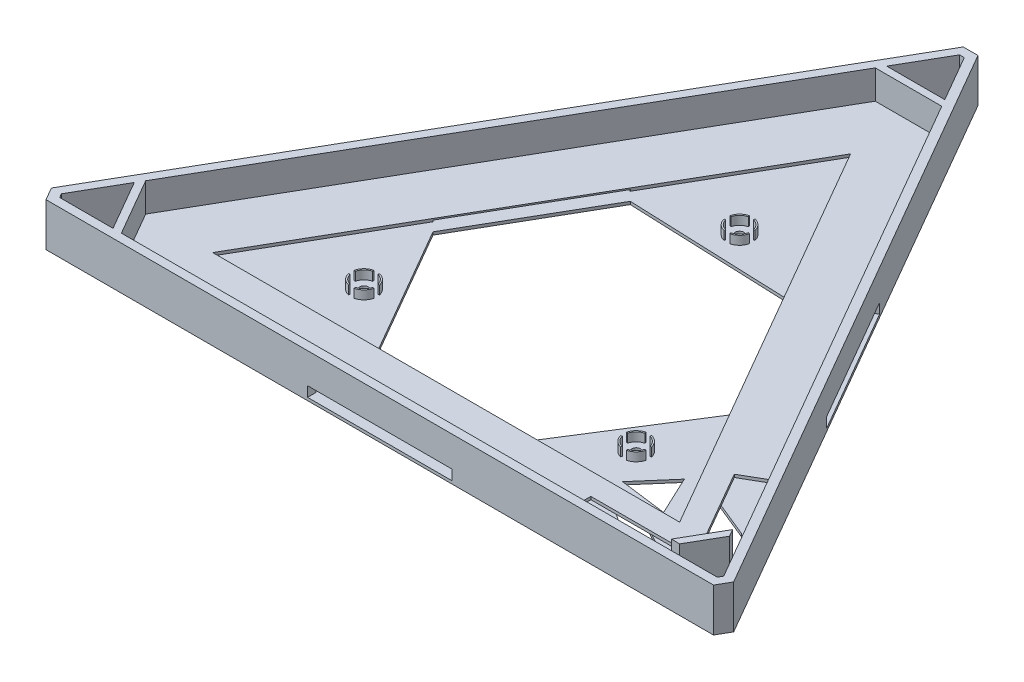
SolidWorks part; units mm, degrees
ref_plane "Front Plane" through (0, 0, 0) normal (0, 0, 1) x (1, 0, 0)
ref_plane "Top Plane" through (0, 0, 0) normal (0, 1, 0) x (1, 0, 0)
ref_plane "Right Plane" through (0, 0, 0) normal (1, 0, 0) x (0, 0, -1)
sketch "Sketch1" plane through (0, 0, 0) normal (0, 1, 0) x (1, 0, 0)
  line L0 (351.2729, 67.6655) -> (468.273, -134.9846)
  line L1 (347.2728, 67.6655) -> (347.2728, 65.1655) construction
  line L2 (409.773, -33.6595) -> (407.6079, -34.9095) construction
  line L3 (468.273, -134.9846) -> (464.2732, -141.9124)
  line L4 (230.2733, -141.9124) -> (464.2732, -141.9124)
  line L5 (230.2733, -141.9124) -> (226.2727, -134.9842)
  line L6 (226.2727, -134.9842) -> (343.2728, 67.6655)
  line L7 (353.4142, 63.9567) -> (351.2491, 62.7067) construction
  line L8 (347.2733, -141.9124) -> (347.2733, -139.4124) construction
  line L9 (231.7167, -139.4124) -> (462.8299, -139.4124)
  line L10 (284.7727, -33.6594) -> (286.9378, -34.9094) construction
  line L11 (344.7161, 65.1655) -> (349.8295, 65.1655)
  line L12 (465.3862, -134.9846) -> (349.8295, 65.1655)
  line L13 (466.2731, -138.4485) -> (464.1081, -137.1985) construction
  line L14 (462.8299, -139.4124) -> (465.3862, -134.9846)
  line L15 (229.1594, -134.9842) -> (344.7161, 65.1655)
  line L16 (229.1594, -134.9842) -> (231.7167, -139.4124)
  line L17 (286.9378, -34.9094) -> (287.3708, -35.1594) construction
  line L18 (230.438, -137.1983) -> (230.871, -136.9483) construction
  line L19 (232.0053, -138.9123) -> (229.7368, -134.9842)
  line L20 (343.2728, 67.6655) -> (351.2729, 67.6655)
  line L21 (345.0048, 64.6655) -> (229.7368, -134.9842)
  line L22 (349.5409, 64.6655) -> (345.0048, 64.6655)
  line L23 (249.0568, -126.4468) -> (246.8918, -127.697) construction
  line L24 (407.6079, -34.9095) -> (407.1749, -35.1595) construction
  line L26 (233.4463, -136.4089) -> (251.9226, -136.4093)
  line L27 (464.8089, -134.9846) -> (462.5412, -138.9123)
  line L28 (462.5412, -138.9123) -> (232.0053, -138.9123)
  line L29 (251.9226, -136.4093) -> (241.8609, -118.9847)
  line L30 (241.8609, -118.9847) -> (232.6236, -134.9842)
  line L31 (232.6236, -134.9842) -> (233.4463, -136.4089)
  line L33 (287.3708, -35.1594) -> (289.5359, -36.4094) construction
  line L34 (254.8093, -136.4089) -> (243.3042, -116.4848)
  line L35 (335.7675, 43.666) -> (243.3042, -116.4848)
  line L36 (358.7782, 43.666) -> (335.7675, 43.666)
  line L38 (289.5359, -36.4094) -> (306.8564, -46.4094) construction
  line L41 (461.939, -134.9846) -> (461.1164, -136.4093)
  line L42 (347.2688, -136.4172) -> (347.2688, -116.4172) construction
  line L43 (442.6021, -136.4093) -> (452.6999, -118.9847)
  line L44 (245.2636, -119.878) -> (249.0568, -126.4468) construction
  line L45 (452.6999, -118.9847) -> (461.939, -134.9846)
  line L48 (461.1164, -136.4093) -> (442.6021, -136.4093)
  line L49 (405.0134, -36.4027) -> (387.6936, -46.404) construction
  line L50 (306.8564, -46.4094) -> (466.2731, -138.4485) construction
  line L51 (357.3348, 46.166) -> (337.2109, 46.166)
  line L52 (337.2109, 46.166) -> (346.4484, 62.1659)
  line L53 (346.4484, 62.1659) -> (348.0966, 62.164)
  line L54 (348.0966, 62.164) -> (357.3348, 46.166)
  line L55 (228.273, -138.4483) -> (387.6936, -46.404) construction
  line L56 (347.2688, -116.4172) -> (347.2728, 43.666) construction
  line L57 (266.4391, -116.428) -> (428.1137, -116.4172)
  line L58 (347.2736, 23.6092) -> (428.1137, -116.4172)
  line L59 (266.4391, -116.428) -> (347.2736, 23.6092)
  line L60 (439.7283, -136.4254) -> (439.7283, -132.9254) construction
  line L61 (451.2487, -116.4715) -> (448.6507, -117.9717) construction
  line L62 (452.6999, -118.9847) -> (358.7782, 43.666)
  line L63 (442.6021, -136.4093) -> (254.8093, -136.4089)
  line L64 (441.749, -132.9254) -> (444.621, -132.9254)
  line L65 (448.6507, -117.9717) -> (450.9647, -121.979) construction
  line L66 (449.5167, -119.4714) -> (450.9647, -121.979)
  line L67 (441.749, -132.9254) -> (449.5167, -119.4714)
  line L68 (450.9647, -121.979) -> (444.621, -132.9254)
  line L69 (461.939, -134.9846) -> (427.2809, -114.9747) construction
  line L70 (461.1164, -136.4093) -> (426.4891, -116.4173) construction
  line L73 (405.0134, -134.9846) -> (439.7283, -134.9846)
  line L74 (405.0134, -134.9846) -> (405.0134, -124.0609)
  line L75 (405.0134, -124.0609) -> (439.7283, -124.0609)
  line L76 (439.7283, -134.9846) -> (439.7283, -124.0609)
  line L77 (405.0134, -124.0609) -> (430.3202, -80.2282) construction
  line L78 (405.0134, -134.9846) -> (433.4739, -85.6896) construction
  line L79 (461.1164, -136.4093) -> (424.3464, -72.7321) construction
  line L80 (432.6513, -87.1143) -> (423.1904, -92.5775)
  line L81 (432.6513, -87.1143) -> (450.1194, -117.365)
  line L82 (423.1904, -92.5775) -> (440.6585, -122.8281)
  line L83 (450.1194, -117.365) -> (440.6585, -122.8281)
  point P13 (407.6079, -34.9095)
  point P20 (464.1081, -137.1985)
  point P23 (347.2733, -139.4124)
  point P25 (347.2732, -141.9124)
  point P27 (347.2728, 65.1655)
  point P31 (286.9378, -34.9094)
  point P37 (287.3708, -35.1594)
  point P39 (230.871, -136.9483)
  point P41 (347.2728, 64.6655)
  point P45 (407.1749, -35.1595)
  point P50 (246.8918, -127.697)
  point P56 (289.5359, -36.4094)
  point P58 (249.0568, -126.4468)
  point P60 (347.2728, 43.666)
  point P62 (345.0048, -136.4089)
  point P64 (445.4885, -126.4485)
  point P71 (447.651, -127.697)
  point P77 (347.2728, 46.166)
  point P84 (347.2688, -116.4172)
  point P87 (387.6936, -46.404)
  point P89 (306.8564, -46.4094)
  point P100 (405.0134, -36.4027)
  dimension "D1" = 2.5
  dimension "D2" = 2.5
  dimension "D3" = 2.5
  dimension "D4" = 2.5
  dimension "D5" = 2.5
  dimension "D6" = 2.5
  dimension "D7" = 0.5
  dimension "D8" = 0.5
  dimension "D9" = 0.5
  dimension "D10" = 2.5
  dimension "D11" = 2.5
  dimension "D12" = 20
  dimension "D13" = 20
  dimension "D14" = 20
  dimension "D15" = 3.5
  dimension "D16" = 3
extrude "Boss-Extrude1" add sketch "Sketch1" along normal blind 1 contours L36 L35 L34 L57 L59 L58 region at (251.4484, 0, 125.0658)
extrude "Boss-Extrude2" add sketch "Sketch1<9>" along normal blind 11 contours L28 L27 L22 L21 L19 L31 L30 L29 L26 L34 L35 L36 L41 L48 L43 L45 L53 L54 L51 L52 | L68 L64 L67 L66 region at (230.7087, 0, 137.042)
sketch "Sketch1<9>" plane through (0, 0, 0) normal (0, 1, 0) x (1, 0, 0) same geometry as "Sketch1"
extrude "Boss-Extrude3" add sketch "Sketch1<10>" along normal blind 5 and the other way blind 3 contours L28 L27 L22 L21 L19 L31 L30 L29 L26 L34 L35 L36 L41 L48 L43 L45 L53 L54 L51 L52 | L68 L64 L67 L66 region at (230.7087, 0, 137.042)
sketch "Sketch1<10>" plane through (0, 0, 0) normal (0, 1, 0) x (1, 0, 0) same geometry as "Sketch1"
sketch "Sketch3" plane through (290.5896, 0, -167.772) normal (0.866, 0, -0.5) x (-0.5, 0, -0.866)
  line L1 (-261.593, -6.5) -> (-211.593, -6.5)
  line L2 (-261.593, -6.5) -> (-261.593, 0.5)
  line L3 (-261.593, 0.5) -> (-211.593, 0.5)
  line L4 (-211.593, -6.5) -> (-211.593, 0.5)
  line L5 (-261.593, -6.5) -> (-211.593, 0.5) construction
  line L6 (-261.593, 0.5) -> (-211.593, -6.5) construction
  point P0 (-236.593, -3)
  dimension "D1" = 50
  dimension "D2" = 7
extrude "Cut-Extrude3" cut sketch "Sketch3" against normal blind 25
sketch "Sketch5" plane through (0, 0, 139.4124) normal (0, 0, 1) x (1, 0, 0)
  line L0 (231.7167, -3) -> (462.8299, -3) construction
  line L1 (322.2733, -6.5) -> (372.2733, -6.5)
  line L2 (322.2733, -6.5) -> (322.2733, 0.5)
  line L3 (322.2733, 0.5) -> (372.2733, 0.5)
  line L4 (372.2733, -6.5) -> (372.2733, 0.5)
  line L5 (322.2733, -6.5) -> (372.2733, 0.5) construction
  line L6 (322.2733, 0.5) -> (372.2733, -6.5) construction
  point P0 (347.2733, -3)
  dimension "D1" = 50
  dimension "D2" = 7
extrude "Cut-Extrude4" cut sketch "Sketch5" against normal blind 25
sketch "Sketch6" plane through (230.3194, 0, 132.9752) normal (-0.866, 0, -0.5) x (-0.5, 0, 0.866)
  line L0 (2.3199, -3) -> (-228.7932, -3) construction
  line L1 (-138.2367, -6.5) -> (-88.2367, -6.5)
  line L2 (-138.2367, -6.5) -> (-138.2367, 0.5)
  line L3 (-138.2367, 0.5) -> (-88.2367, 0.5)
  line L4 (-88.2367, -6.5) -> (-88.2367, 0.5)
  line L5 (-138.2367, -6.5) -> (-88.2367, 0.5) construction
  line L6 (-138.2367, 0.5) -> (-88.2367, -6.5) construction
  point P0 (-113.2367, -3)
  dimension "D1" = 50
  dimension "D2" = 7
extrude "Cut-Extrude5" cut sketch "Sketch6" against normal blind 25
sketch "Sketch8" plane through (0, -3, 0) normal (0, -1, 0) x (1, 0, 0)
  line L1 (349.8295, -65.1655) -> (465.3862, 134.9846)
  line L2 (465.3862, 134.9846) -> (462.8299, 139.4124)
  line L3 (414.7932, 116.4181) -> (444.621, 132.9254)
  line L4 (444.621, 132.9254) -> (450.9647, 121.979)
  line L6 (462.8299, 139.4124) -> (231.7167, 139.4124)
  line L9 (452.6999, 118.9847) -> (461.939, 134.9846)
  line L12 (461.939, 134.9846) -> (461.1164, 136.4093)
  line L15 (450.9647, 121.979) -> (444.621, 132.9254) construction
  line L17 (461.1164, 136.4093) -> (442.6021, 136.4093)
  line L19 (322.2733, 116.4243) -> (294.3582, 68.0611)
  line L20 (294.3582, 68.0611) -> (319.3545, 24.7577)
  line L21 (319.3545, 24.7577) -> (376.4737, 26.9694)
  line L22 (376.4737, 26.9694) -> (401.4727, 70.2712)
  line L23 (401.4727, 70.2712) -> (372.2733, 116.4209)
  line L24 (372.2733, 116.4209) -> (322.2733, 116.4243)
  line L25 (386.873, 93.3461) -> (395.3235, 98.6928) construction
  line L30 (308.3157, 92.2427) -> (299.6549, 97.2417) construction
  line L31 (347.9141, 25.8635) -> (348.3013, 15.8635) construction
  line L37 (231.7167, 139.4124) -> (229.1594, 134.9842)
  line L39 (233.4463, 136.4089) -> (251.9226, 136.4093)
  line L40 (251.9226, 136.4093) -> (241.8609, 118.9847)
  line L41 (241.8609, 118.9847) -> (232.6236, 134.9842)
  line L42 (232.6236, 134.9842) -> (233.4463, 136.4089)
  line L43 (349.8295, -65.1655) -> (344.7161, -65.1655)
  line L44 (344.7161, -65.1655) -> (229.1594, 134.9842)
  line L45 (337.2109, -46.166) -> (357.3348, -46.166)
  line L46 (357.3348, -46.166) -> (348.0966, -62.164)
  line L47 (348.0966, -62.164) -> (346.4484, -62.1659)
  line L48 (346.4484, -62.1659) -> (337.2109, -46.166)
  line L50 (450.9647, 121.979) -> (423.7433, 108.847)
  line L53 (442.6021, 136.4093) -> (432.3028, 135.575)
  line L54 (432.3028, 135.575) -> (404.0131, 116.4188)
  line L55 (416.4531, 96.2194) -> (438.0861, 105.0562)
  line L57 (404.0131, 116.4188) -> (414.7932, 116.4181)
  line L58 (416.4531, 96.2194) -> (423.7433, 108.847)
  line L59 (372.2733, 116.4209) -> (428.1137, 116.4172) construction
  line L60 (401.4727, 70.2712) -> (428.1137, 116.4172) construction
  line L61 (438.0861, 105.0562) -> (452.6999, 118.9847)
  line L62 (418.4238, 112.3006) -> (412.03, 98.6928)
  line L63 (412.03, 98.6928) -> (402.0841, 110.1693)
  line L64 (402.0841, 110.1693) -> (418.4238, 112.3006)
  circle A0 centre (395.3235, 98.6928) radius 1.5
  circle A1 centre (348.3013, 15.8635) radius 1.5
  circle A2 centre (299.6549, 97.2417) radius 1.5
  dimension "D6" = 3
  dimension "D7" = 3
  dimension "D8" = 3
  dimension "D3" = 10
  dimension "D4" = 10
  dimension "D5" = 10
extrude "Boss-Extrude5" add sketch "Sketch8" along normal blind 1
sketch "Sketch12" plane through (0, -3, 0) normal (0, 1, 0) x (1, 0, 0)
  line L0 (348.3013, -11.8635) -> (348.3013, -11.3635) construction
  line L1 (348.3013, -11.3635) -> (349.2951, -11.4746) construction
  line L2 (349.2951, -11.4746) -> (349.1847, -11.9623)
  line L3 (348.3013, -11.3635) -> (347.3075, -11.4746) construction
  line L4 (347.3075, -11.4746) -> (347.4179, -11.9623)
  line L5 (352.3013, -15.8635) -> (352.8013, -15.8635) construction
  line L6 (344.3013, -15.8635) -> (343.8013, -15.8635) construction
  line L7 (348.3013, -19.8635) -> (348.3013, -20.3635) construction
  line L8 (352.8013, -15.8635) -> (352.6902, -14.8697) construction
  line L9 (352.8013, -15.8635) -> (352.6902, -16.8573) construction
  line L10 (343.8013, -15.8635) -> (343.9124, -14.8697) construction
  line L11 (343.8013, -15.8635) -> (343.9124, -16.8573) construction
  line L12 (348.3013, -20.3635) -> (349.2951, -20.2524) construction
  line L13 (348.3013, -20.3635) -> (347.3075, -20.2524) construction
  line L14 (343.9124, -14.8697) -> (348.3013, -15.8635) construction
  line L15 (348.3013, -15.8635) -> (352.6902, -14.8697) construction
  line L16 (343.9124, -16.8573) -> (348.3013, -15.8635) construction
  line L17 (348.3013, -15.8635) -> (352.6902, -16.8573) construction
  line L18 (347.3075, -20.2524) -> (348.3013, -15.8635) construction
  line L19 (348.3013, -15.8635) -> (349.2951, -20.2524) construction
  line L20 (343.9124, -14.8697) -> (344.4001, -14.9801)
  line L21 (343.9124, -16.8573) -> (344.4001, -16.7469)
  line L22 (347.3075, -20.2524) -> (347.4179, -19.7648)
  line L23 (349.2951, -20.2524) -> (349.1847, -19.7648)
  line L24 (352.6902, -14.8697) -> (352.2025, -14.9801)
  line L25 (352.6902, -16.8573) -> (352.2025, -16.7469)
  line L26 (395.3235, -94.1928) -> (395.3235, -98.6928) construction
  line L27 (395.3235, -98.6928) -> (390.8235, -98.6928) construction
  line L28 (390.8235, -98.6928) -> (390.9347, -97.699) construction
  line L29 (399.8235, -98.6928) -> (395.3235, -98.6928) construction
  line L30 (395.3235, -98.6928) -> (395.3235, -103.1928) construction
  line L31 (395.3235, -103.1928) -> (396.3173, -103.0817) construction
  line L32 (395.3235, -94.1928) -> (396.3173, -94.3039) construction
  line L33 (395.3235, -94.1928) -> (394.3297, -94.3039) construction
  line L34 (399.7124, -97.699) -> (399.8235, -98.6928) construction
  line L35 (399.8235, -98.6928) -> (399.7124, -99.6866) construction
  line L36 (390.9347, -99.6866) -> (390.8235, -98.6928) construction
  line L37 (394.3297, -103.0817) -> (395.3235, -103.1928) construction
  line L38 (394.3297, -94.3039) -> (395.3235, -98.6928) construction
  line L39 (395.3235, -98.6928) -> (396.3173, -94.3039) construction
  line L40 (390.9347, -99.6866) -> (395.3235, -98.6928) construction
  line L41 (395.3235, -98.6928) -> (390.9347, -97.699) construction
  line L42 (399.7124, -97.699) -> (395.3235, -98.6928) construction
  line L43 (395.3235, -98.6928) -> (399.7124, -99.6866) construction
  line L44 (394.3297, -103.0817) -> (395.3235, -98.6928) construction
  line L45 (395.3235, -98.6928) -> (396.3173, -103.0817) construction
  line L46 (394.3297, -94.3039) -> (394.4402, -94.7916)
  line L47 (396.3173, -94.3039) -> (396.2069, -94.7916)
  line L48 (399.7124, -97.699) -> (399.2248, -97.8094)
  line L49 (399.7124, -99.6866) -> (399.2248, -99.5762)
  line L50 (396.3173, -103.0817) -> (396.2069, -102.5941)
  line L51 (394.3297, -103.0817) -> (394.4402, -102.5941)
  line L52 (390.9347, -99.6866) -> (391.4223, -99.5762)
  line L53 (390.9347, -97.699) -> (391.4248, -97.7985)
  line L54 (299.6549, -92.7417) -> (299.6549, -97.2417) construction
  line L55 (299.6549, -97.2417) -> (304.1549, -97.2417) construction
  line L56 (299.6549, -101.7417) -> (299.6549, -97.2417) construction
  line L57 (299.6549, -97.2417) -> (295.1549, -97.2417) construction
  line L58 (299.6549, -97.2417) -> (298.6611, -92.8528) construction
  line L59 (298.6611, -92.8528) -> (299.6549, -92.7417) construction
  line L60 (299.6549, -92.7417) -> (300.6487, -92.8528) construction
  line L61 (300.6487, -92.8528) -> (299.6549, -97.2417) construction
  line L62 (299.6549, -97.2417) -> (304.0438, -96.2479) construction
  line L63 (304.0438, -96.2479) -> (304.1549, -97.2417) construction
  line L64 (304.1549, -97.2417) -> (304.0438, -98.2355) construction
  line L65 (304.0438, -98.2355) -> (299.6549, -97.2417) construction
  line L66 (299.6549, -97.2417) -> (300.6487, -101.6306) construction
  line L67 (300.6487, -101.6306) -> (299.6549, -101.7417) construction
  line L68 (299.6549, -101.7417) -> (298.6611, -101.6306) construction
  line L69 (298.6611, -101.6306) -> (299.6549, -97.2417) construction
  line L70 (299.6549, -97.2417) -> (295.266, -98.2355) construction
  line L71 (295.266, -98.2355) -> (295.1549, -97.2417) construction
  line L72 (295.1549, -97.2417) -> (295.266, -96.2479) construction
  line L73 (295.266, -96.2479) -> (299.6549, -97.2417) construction
  line L74 (295.266, -96.2479) -> (295.7537, -96.3583)
  line L75 (295.266, -98.2355) -> (295.7537, -98.1251)
  line L76 (298.6611, -101.6306) -> (298.7715, -101.1429)
  line L77 (300.6487, -101.6306) -> (300.5383, -101.1429)
  line L78 (304.0438, -98.2355) -> (303.5561, -98.1251)
  line L79 (304.0438, -96.2479) -> (303.5561, -96.3583)
  line L80 (300.6487, -92.8528) -> (300.5383, -93.3404)
  line L81 (298.6611, -92.8528) -> (298.7715, -93.3404)
  circle A0 centre (348.3013, -15.8635) radius 4.5
  circle A1 centre (395.3235, -98.6928) radius 4.5
  circle A2 centre (299.6549, -97.2417) radius 4.5
  circle A3 centre (348.3013, -15.8635) radius 4
  circle A4 centre (395.3235, -98.6928) radius 4
  circle A5 centre (299.6549, -97.2417) radius 4
  dimension "D1" = 9
  dimension "D2" = 9
  dimension "D3" = 9
  dimension "D4" = 8
  dimension "D5" = 8
  dimension "D6" = 8
  dimension "D7" = 1
  dimension "D8" = 1
  dimension "D9" = 1
  dimension "D10" = 1
  dimension "D11" = 1
  dimension "D12" = 1
  dimension "D13" = 1
  dimension "D14" = 1
  dimension "D15" = 1
  dimension "D16" = 1
  dimension "D17" = 1
  dimension "D18" = 1
  dimension "D19" = 1
  dimension "D20" = 1
  dimension "D21" = 1
  dimension "D22" = 1
  dimension "D23" = 1
  dimension "D24" = 1
  dimension "D25" = 1
  dimension "D26" = 1
  dimension "D27" = 1
  dimension "D28" = 1
  dimension "D29" = 1
  dimension "D30" = 1
extrude "Boss-Extrude10" add sketch "Sketch12" along normal blind 3 contours A3 L4 A0 L20 | A3 L24 A0 L2 | A3 L23 A0 L25 | A3 L21 A0 L22 | A4 L46 A1 L53 | A4 L48 A1 L47 | A4 L50 A1 L49 | A4 L52 A1 L51 | A5 L81 A2 L74 | A5 L79 A2 L80 | A5 L77 A2 L78 | A5 L75 A2 L76 region at (351.1537, -3, 13.0111) region at (345.4489, -3, 13.0111) region at (351.1537, -3, 18.7159) region at (345.4489, -3, 18.7159) region at (392.4726, -3, 95.8382) region at (398.1759, -3, 95.8404) region at (392.4712, -3, 101.5452) region at (398.1759, -3, 101.5452) region at (296.8025, -3, 94.3893) region at (296.8025, -3, 100.0941) region at (302.5073, -3, 94.3893) region at (302.5073, -3, 100.0941)
